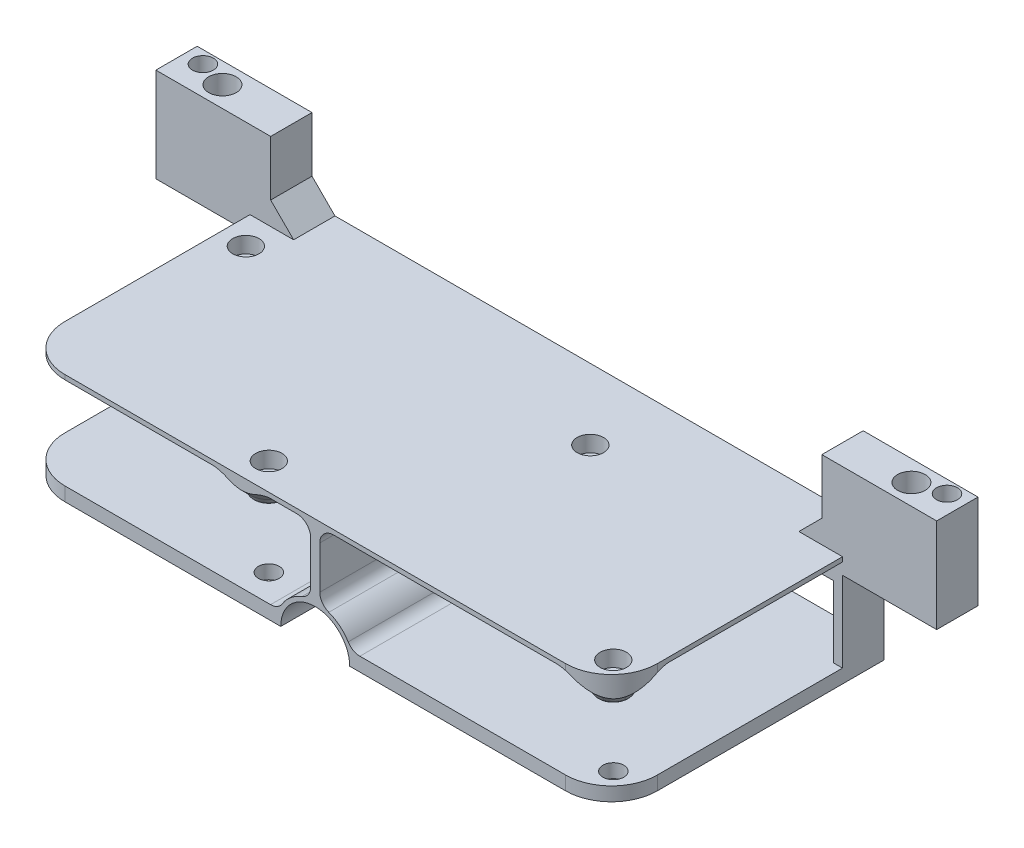
SolidWorks part; units mm, degrees
material "ABS"
ref_plane "Top Plane" through (0, 0, 0) normal (0, 0, 1) x (1, 0, 0)
ref_plane "Front Plane" through (0, 0, 0) normal (0, 1, 0) x (1, 0, 0)
ref_plane "Right Plane" through (0, 0, 0) normal (1, 0, 0) x (0, 0, -1)
sketch "Sketch1" plane through (0, 0, 0) normal (0, 0, 1) x (1, 0, 0)
  line L0 (-85, 18.2915) -> (85, 18.2915)
  line L1 (-85, 18.2915) -> (-85, -2.2085)
  line L2 (-85, -2.2085) -> (-64.5, -2.2085)
  line L3 (85, 18.2915) -> (85, -2.2085)
  line L4 (85, -2.2085) -> (64.5, -2.2085)
  line L5 (-64.5, -2.2085) -> (-64.5, -22.7085)
  line L6 (-64.5, -22.7085) -> (64.5, -22.7085)
  line L9 (64.5, -22.7085) -> (64.5, -2.2085)
  point P3 (0, 18.2915)
  point P8 (64.5, -22.7085)
  point P10 (0, 0)
  dimension "D1" = 170
  dimension "D2" = 20.5
  dimension "D3" = 20.5
  dimension "D4" = 20.5
  dimension "D5" = 20.5
  dimension "D6" = 20.5
extrude "Base-shape" add sketch "Sketch1" along normal blind 9
sketch "Sketch7" plane through (0, 18.2915, 0) normal (0, 1, 0) x (1, 0, 0)
  circle A0 centre (-75, -4.5) radius 1.75
  circle A1 centre (75, -4.5) radius 1.75
  dimension "D5" = 3.5
  dimension "D6" = 3.5
  dimension "D1" = 4.5
  dimension "D2" = 4.5
  dimension "D3" = 150
  dimension "D4" = 75
extrude "frame-mount-holes" cut sketch "Sketch7" against normal through all
sketch "Sketch8" plane through (0, 18.2915, 0) normal (0, 1, 0) x (1, 0, 0)
  circle A0 centre (-75, -4.5) radius 3
  circle A1 centre (75, -4.5) radius 3
  dimension "D1" = 6
  dimension "D2" = 6
extrude "frame-mount-headsinks" cut sketch "Sketch8" against normal blind 14
sketch "Sketch9" plane through (0, 18.2915, 0) normal (0, 1, 0) x (1, 0, 0)
  line L0 (85, 0) -> (-85, 0) construction
  line L1 (-60, 0) -> (60, 0)
  line L2 (-60, 0) -> (-60, -9)
  line L3 (-60, -9) -> (60, -9)
  line L4 (60, 0) -> (60, -9)
  line L5 (85, -9) -> (-85, -9) construction
  line L6 (-85, -9) -> (-85, 0) construction
  line L7 (85, -9) -> (85, 0) construction
  dimension "D1" = 25
  dimension "D2" = 25
extrude "brush-cutout" cut sketch "Sketch9" against normal blind 17
chamfer "Chamfer1" distance 5 angle 45 2 edges at (60, 1.2915, 4.5) (-60, 1.2915, 4.5)
sketch "Sketch11" plane through (0, 18.2915, 0) normal (0, 1, 0) x (1, 0, 0)
  line L0 (-60, 0) -> (-85, 0) construction
  line L1 (85, 0) -> (60, 0) construction
  line L2 (-85, -9) -> (-85, 0) construction
  line L3 (85, -9) -> (85, 0) construction
  circle A0 centre (-81, -2.75) radius 2.275
  circle A1 centre (81, -2.75) radius 2.275
  point P0 (-81, -2.75)
  point P1 (81, -2.75)
  dimension "D5" = 4.55
  dimension "D6" = 4.55
  dimension "D1" = 2.75
  dimension "D2" = 2.75
  dimension "D3" = 4
  dimension "D4" = 4
extrude "bedsheet stoppers" cut sketch "Sketch11" against normal blind 10
sketch "Sketch12" plane through (0, -2.2085, 0) normal (0, -1, 0) x (1, 0, 0)
  circle A0 centre (-75, -6.5) radius 8
  circle A1 centre (75, -6) radius 7.5
  dimension "D2" = 16
  dimension "D3" = 15
  dimension "D1" = 150
  dimension "D4" = 75
  dimension "D5" = 6.5
  dimension "D6" = 6
extrude "bed mount screw spacer" cut sketch "Sketch12" against normal blind 5
sketch "Sketch13" plane through (0, 0, 9) normal (0, 0, 1) x (1, 0, 0)
  line L0 (-64.5, -22.7085) -> (64.5, -22.7085) construction
  line L1 (42.5, -4.2085) -> (62.5, -4.2085)
  line L2 (42.5, -4.2085) -> (42.5, -19.7085)
  line L3 (42.5, -19.7085) -> (62.5, -19.7085)
  line L4 (62.5, -4.2085) -> (62.5, -19.7085)
  line L5 (-32.5, -4.2085) -> (-12.5, -4.2085)
  line L6 (-32.5, -4.2085) -> (-32.5, -19.7085)
  line L7 (-32.5, -19.7085) -> (-12.5, -19.7085)
  line L8 (-12.5, -4.2085) -> (-12.5, -19.7085)
  line L9 (-64.5, -2.2085) -> (-64.5, -22.7085) construction
  line L10 (64.5, -22.7085) -> (64.5, -2.2085) construction
  dimension "D1" = 3
  dimension "D2" = 3
  dimension "D3" = 15.5
  dimension "D4" = 15.5
  dimension "D5" = 20
  dimension "D6" = 20
  dimension "D7" = 52
  dimension "D8" = 2
extrude "fan cutouts" cut sketch "Sketch13" against normal through all
sketch "Sketch15" plane through (0, 0, 9) normal (0, 0, 1) x (1, 0, 0)
  line L0 (64.5, -22.7085) -> (64.5, -2.2085) construction
  line L1 (-64.5, -22.7085) -> (64.5, -22.7085)
  line L2 (-64.5, -22.7085) -> (-64.5, -19.7085)
  line L3 (-64.5, -19.7085) -> (64.5, -19.7085)
  line L4 (64.5, -22.7085) -> (64.5, -19.7085)
  line L6 (-64.5, 0.2915) -> (64.5, 0.2915)
  line L7 (-64.5, 0.2915) -> (-64.5, 1.2915)
  line L8 (-64.5, 1.2915) -> (64.5, 1.2915)
  line L9 (64.5, 0.2915) -> (64.5, 1.2915)
  dimension "D1" = 3
  dimension "D2" = 1
  dimension "D3" = 20
extrude "fan mount plates" add sketch "Sketch15" along normal blind 50.3
fillet "outer fillet" radius 10 4 edges at (64.5, -21.2085, 59.3) (-64.5, -21.2085, 59.3) (64.5, 0.7915, 59.3) (-64.5, 0.7915, 59.3)
sketch "Sketch16" plane through (0, -19.7085, 0) normal (0, 1, 0) x (1, 0, 0)
  line L0 (-32.5, -9) -> (-64.5, -9) construction
  line L1 (42.5, -9) -> (-12.5, -9) construction
  line L2 (62.5, 0) -> (62.5, -9) construction
  line L3 (-12.5, 0) -> (-12.5, -9) construction
  circle A0 centre (-16, -53.4) radius 2.275
  circle A1 centre (59, -53.4) radius 2.275
  circle A2 centre (-59, -15.4) radius 2.275
  circle A3 centre (16, -15.4) radius 2.275
  point P0 (36, -33.4)
  point P1 (-39, -33.4)
  point P10 (-12.5, -4.5)
  point P11 (59, -53.4)
  point P12 (-16, -53.4)
  point P21 (-59, -2.6)
  point P23 (36, -33.4)
  dimension "D9" = 4.55
  dimension "D10" = 4.55
  dimension "D11" = 4.55
  dimension "D12" = 4.55
  dimension "D1" = 24.4
  dimension "D2" = 24.4
  dimension "D3" = 26.5
  dimension "D4" = 26.5
  dimension "D5" = 20
  dimension "D6" = 20
  dimension "D7" = 23
  dimension "D8" = 23
  dimension "D13" = 20
  dimension "D14" = 18
  dimension "D15" = 20
  dimension "D16" = 18
extrude "fan mount holes - base" cut sketch "Sketch16" against normal through all and the other way through all
sketch "Sketch18" plane through (0, 0.2915, 0) normal (0, -1, 0) x (1, 0, 0)
  circle A0 centre (-16, 53.4) radius 1.75
  circle A1 centre (16, 15.4) radius 1.75
  circle A2 centre (-59, 15.4) radius 1.75
  circle A3 centre (59, 53.4) radius 1.75
  circle A4 centre (-16, 53.4) radius 3.5
  circle A5 centre (59, 53.4) radius 3.5
  circle A6 centre (16, 15.4) radius 3.5
  circle A7 centre (-59, 15.4) radius 3.5
  dimension "D1" = 3.5
  dimension "D2" = 3.5
  dimension "D3" = 3.5
  dimension "D4" = 3.5
  dimension "D5" = 7
  dimension "D6" = 7
  dimension "D7" = 7
  dimension "D8" = 7
extrude "fan mounts lid" add sketch "Sketch18" along normal blind 5
sketch "Sketch19" plane through (0, 1.2915, 0) normal (0, 1, 0) x (1, 0, 0)
  circle A0 centre (-59, -15.4) radius 2.875
  circle A1 centre (-16, -53.4) radius 2.875
  circle A2 centre (59, -53.4) radius 2.875
  circle A3 centre (16, -15.4) radius 2.875
  dimension "D1" = 5.75
  dimension "D2" = 5.75
  dimension "D3" = 5.75
  dimension "D4" = 5.75
extrude "fanmount head sinks" cut sketch "Sketch19" against normal blind 3.5
chamfer "fanmount champfers" distance 4 angle 45 4 edges at (59, 0.2915, 56.9) (-59, 0.2915, 18.9) (16, 0.2915, 18.9) (-16, 0.2915, 56.9)
fillet "fanmount fillets1" radius 1 4 edges at (-59, -4.7085, 11.9) (59, -4.7085, 49.9) (-16, -4.7085, 49.9) (16, -4.7085, 11.9)
fillet "fanmount fillets 2" radius 4 4 edges at (59, -3.7085, 56.9) (-16, -3.7085, 56.9) (16, -3.7085, 18.9) (-59, -3.7085, 18.9)
fillet "fanmount fillets 3" radius 3 4 edges at (53.4833, 0.2915, 48.319) (16, 0.2915, 22.9) (-16, 0.2915, 45.9) (-53.1958, 0.2915, 20.1499)
sketch "Sketch20" plane through (0, 0, 0) normal (0, 0, -1) x (-1, 0, 0)
  line L0 (64.5, -22.7085) -> (-64.5, -22.7085) construction
  circle A0 centre (0, -22.7085) radius 7.5
extrude "cablespace" cut sketch "Sketch20" against normal through all
sketch "Sketch21" plane through (0, 0, 9) normal (0, 0, 1) x (1, 0, 0)
  line L0 (-1, 0.2915) -> (-1, -14.3421)
  line L1 (-53.044, 0.2915) -> (10.044, 0.2915) construction
  line L2 (-1, 0.2915) -> (1, 0.2915)
  line L3 (1, 0.2915) -> (1, -14.3421)
  line L4 (-6.8739, -19.7085) -> (-7.8739, -19.7085)
  line L5 (-6.8739, -19.7085) -> (-12.5, -19.7085) construction
  line L6 (6.8739, -19.7085) -> (7.8739, -19.7085)
  line L7 (42.5, -19.7085) -> (6.8739, -19.7085) construction
  arc A2 (6.8739, -19.7085) -> (-6.8739, -19.7085) centre (0, -22.7085) ccw
  arc A3 (6.8739, -19.7085) -> (-6.8739, -19.7085) centre (0, -22.7085) ccw
  arc A4 (-7.8739, -19.7085) -> (-1, -14.3421) centre (0, -22.7085) cw
  arc A5 (1, -14.3421) -> (7.8739, -19.7085) centre (0, -22.7085) cw
  point P9 (7.8739, -19.6988)
  point P18 (7.8739, -19.7085)
  dimension "D2" = 1
  dimension "D3" = 2
  dimension "D4" = 1
  dimension "D5" = 1
  dimension "D1" = 0
extrude "middle-stabilizer" add sketch "Sketch21" along normal blind 50.3
fillet "middle stabilizer fillets" radius 3 6 edges at (7.8739, -19.7085, 34.15) (-7.8739, -19.7085, 34.15) (-1, -14.3421, 34.15) (1, -14.3421, 34.15) (-1, 0.2915, 34.15) (1, 0.2915, 34.15)
